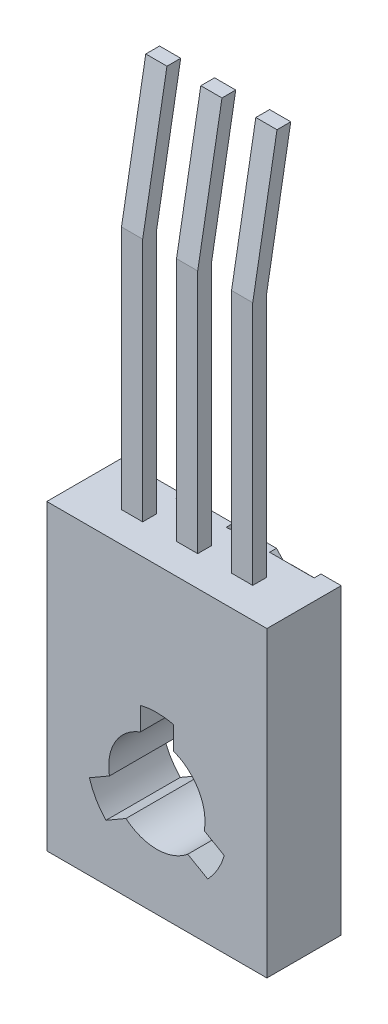
SolidWorks part; units mm, degrees
ref_plane "Front Plane" through (0, 0, 0) normal (0, 0, 1) x (1, 0, 0)
ref_plane "Top Plane" through (0, 0, 0) normal (0, 1, 0) x (1, 0, 0)
ref_plane "Right Plane" through (0, 0, 0) normal (1, 0, 0) x (0, 0, -1)
sketch "Sketch1" plane through (0, 0, 0) normal (0, 0, 1) x (1, 0, 0)
  line L1 (-4, 5.5) -> (4, 5.5)
  line L2 (-4, 5.5) -> (-4, -5.5)
  line L3 (-4, -5.5) -> (4, -5.5)
  line L4 (4, 5.5) -> (4, -5.5)
  line L5 (-4, 5.5) -> (4, -5.5) construction
  line L6 (-4, -5.5) -> (4, 5.5) construction
  circle A0 centre (0, -1.7) radius 2.555
  point P0 (0, 0)
  dimension "D3" = 5.11
  dimension "D1" = 11
  dimension "D2" = 8
  dimension "D4" = 3.8
extrude "Boss-Extrude1" add sketch "Sketch1" along normal mid plane 2.7
sketch "Sketch2" plane through (0, 5.5, 0) normal (0, 1, 0) x (1, 0, 0)
  line L0 (0, 0.8819) -> (0, -0.7814) construction
  line L1 (-0.385, 0.25) -> (0.385, 0.25)
  line L2 (-0.385, 0.25) -> (-0.385, -0.25)
  line L3 (-0.385, -0.25) -> (0.385, -0.25)
  line L4 (0.385, 0.25) -> (0.385, -0.25)
  line L5 (-0.385, 0.25) -> (0.385, -0.25) construction
  line L6 (-0.385, -0.25) -> (0.385, 0.25) construction
  line L7 (-2.385, 0.25) -> (-1.615, 0.25)
  line L8 (-2.385, 0.25) -> (-2.385, -0.25)
  line L9 (-2.385, -0.25) -> (-1.615, -0.25)
  line L10 (-1.615, 0.25) -> (-1.615, -0.25)
  line L11 (-2.385, 0.25) -> (-1.615, -0.25) construction
  line L12 (-2.385, -0.25) -> (-1.615, 0.25) construction
  line L13 (2.385, -0.25) -> (1.615, -0.25)
  line L14 (1.615, 0.25) -> (1.615, -0.25)
  line L15 (2.385, 0.25) -> (1.615, 0.25)
  line L16 (2.385, 0.25) -> (2.385, -0.25)
  point P0 (0, 0)
  point P7 (-2, 0)
  dimension "D1" = 0.5
  dimension "D2" = 0.77
  dimension "D3" = 0.77
  dimension "D4" = 0.5
  dimension "D5" = 2
extrude "Boss-Extrude2" add sketch "Sketch2" along normal blind 8.9
sketch "Sketch4" plane through (0, 0, 1.35) normal (0, 0, 1) x (1, 0, 0)
  line L0 (0, 0.8936) -> (0, -1.7) construction
  line L3 (-0.6, 0.8232) -> (-0.6, -0.0561)
  line L4 (0.6, 0.8232) -> (0.6, -0.0561)
  line L5 (2.4852, -2.442) -> (1.7237, -2.0023)
  line L6 (1.8852, -3.4812) -> (1.1237, -3.0416)
  line L7 (-1.8852, -3.4812) -> (-1.1237, -3.0416)
  line L8 (-2.4852, -2.442) -> (-1.7237, -2.0023)
  arc A0 (-1.1237, -3.0416) -> (1.1237, -3.0416) centre (0, -1.7) ccw
  arc A1 (-1.8852, -3.4812) -> (1.8852, -3.4812) centre (0, -1.7) ccw
  arc A2 (-0.6, -0.0561) -> (-1.7237, -2.0023) centre (0, -1.7) ccw
  arc A3 (-0.6, 0.8232) -> (-2.4852, -2.442) centre (0, -1.7) ccw
  arc A4 (1.7237, -2.0023) -> (0.6, -0.0561) centre (0, -1.7) ccw
  arc A5 (2.4852, -2.442) -> (0.6, 0.8232) centre (0, -1.7) ccw
  point P22 (0, -1.7)
  dimension "D1" = 3.5
  dimension "D2" = 0.6
  dimension "D3" = 3
extrude "Boss-Extrude3" add sketch "Sketch4" against normal up to surface (2.7 mm away) up to face at (0, 0, -1.35)
sketch "Sketch5" plane through (0, 0, -1.35) normal (0, 0, -1) x (-1, 0, 0)
  text T0 "B772" font "Century Gothic" height in points 9
extrude "Cut-Extrude1" cut sketch "Sketch5" against normal blind 0.25
sketch "Sketch6" plane through (0, 14.4, 0) normal (0, 1, 0) x (1, 0, 0)
  line L0 (2.385, -0.25) -> (2.385, 0.25) construction
  line L1 (2.385, 0.25) -> (1.615, 0.25) construction
  line L2 (1.615, 0.25) -> (1.615, -0.25) construction
  line L3 (1.615, -0.25) -> (2.385, -0.25) construction
  line L4 (0.385, -0.25) -> (0.385, 0.25) construction
  line L5 (0.385, 0.25) -> (-0.385, 0.25) construction
  line L6 (-0.385, 0.25) -> (-0.385, -0.25) construction
  line L7 (-0.385, -0.25) -> (0.385, -0.25) construction
  line L8 (-1.615, -0.25) -> (-1.615, 0.25) construction
  line L9 (-1.615, 0.25) -> (-2.385, 0.25) construction
  line L10 (-2.385, 0.25) -> (-2.385, -0.25) construction
  line L11 (-2.385, -0.25) -> (-1.615, -0.25) construction
  line L12 (2.385, -0.25) -> (2.385, 0.25)
  line L13 (2.385, 0.25) -> (1.615, 0.25)
  line L14 (1.615, 0.25) -> (1.615, -0.25)
  line L15 (1.615, -0.25) -> (2.385, -0.25)
  line L16 (0.385, -0.25) -> (0.385, 0.25)
  line L17 (0.385, 0.25) -> (-0.385, 0.25)
  line L18 (-0.385, 0.25) -> (-0.385, -0.25)
  line L19 (-0.385, -0.25) -> (0.385, -0.25)
  line L20 (-1.615, -0.25) -> (-1.615, 0.25)
  line L21 (-1.615, 0.25) -> (-2.385, 0.25)
  line L22 (-2.385, 0.25) -> (-2.385, -0.25)
  line L23 (-2.385, -0.25) -> (-1.615, -0.25)
sketch "Sketch7" plane through (0, 0, 0) normal (1, 0, 0) x (0, 0, -1)
  line L0 (0, 14.4) -> (0.8821, 19.4028)
  line L1 (0.25, 14.4) -> (-0.25, 14.4) construction
  line L2 (-0.25, 14.4) -> (-0.25, 5.5) construction
  dimension "D1" = 10
  dimension "D2" = 5.08
sweep "Sweep1" add profiles "Sketch6" path "Sketch7"
